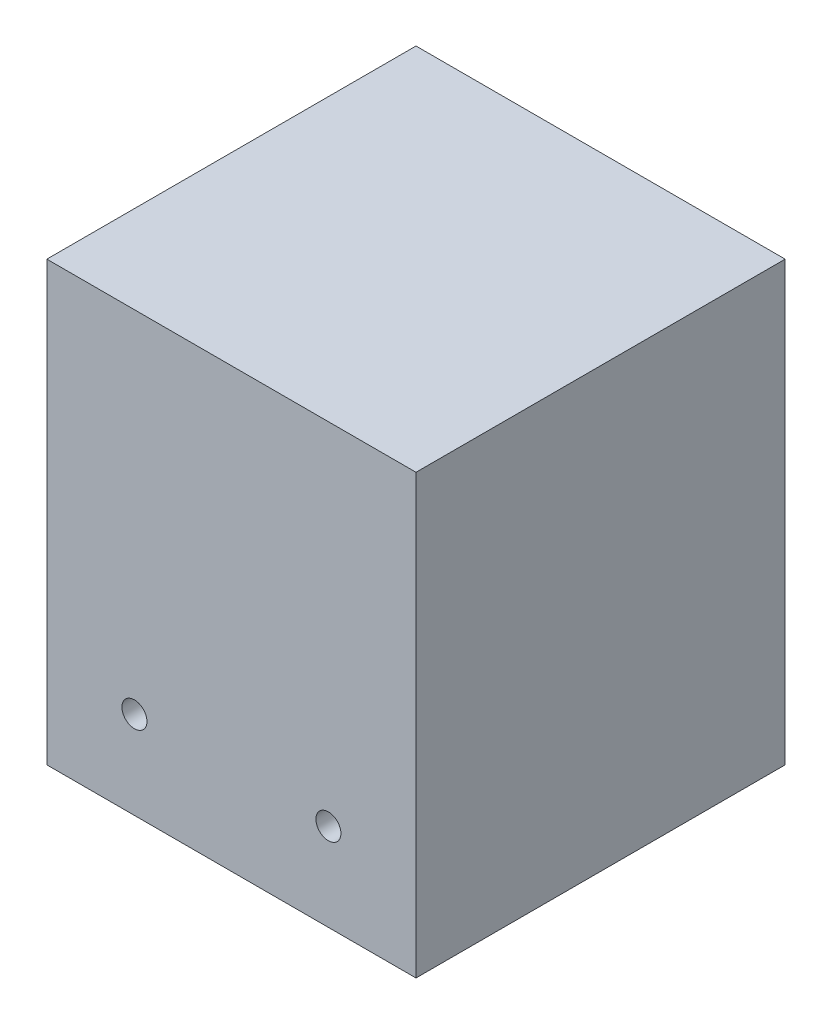
SolidWorks part; units mm, degrees
ref_plane "Plan de face" through (0, 0, 0) normal (0, 0, 1) x (1, 0, 0)
ref_plane "Plan de dessus" through (0, 0, 0) normal (0, 1, 0) x (1, 0, 0)
ref_plane "Plan de droite" through (0, 0, 0) normal (1, 0, 0) x (0, 0, -1)
sketch "Esquisse1" plane through (0, 0, 0) normal (0, 1, 0) x (1, 0, 0)
  line L1 (-29.291, 17.4415) -> (29.709, 17.4415)
  line L2 (-29.291, 17.4415) -> (-29.291, -41.5585)
  line L3 (-29.291, -41.5585) -> (29.709, -41.5585)
  line L4 (29.709, 17.4415) -> (29.709, -41.5585)
  dimension "D1" = 59
  dimension "D2" = 59
extrude "Boss.-Extru.1" add sketch "Esquisse1" along normal blind 70
sketch "Esquisse2" plane through (0, 0, 41.5585) normal (0, 0, 1) x (1, 0, 0)
  line L0 (29.709, 14) -> (15.709, 14) construction
  line L1 (29.709, 70) -> (29.709, 0) construction
  line L2 (15.709, 14) -> (-15.291, 14) construction
  line L3 (-15.291, 14) -> (-29.291, 14) construction
  line L4 (-29.291, 70) -> (-29.291, 0) construction
  line L5 (15.709, 14) -> (15.709, 0) construction
  line L6 (-29.291, 0) -> (29.709, 0) construction
  line L7 (-15.291, 14) -> (-15.291, 0) construction
  circle A0 centre (-15.291, 14) radius 2
  circle A1 centre (15.709, 14) radius 2
  dimension "D1" = 4
  dimension "D2" = 14
extrude "Enlèv. mat.-Extru.1" cut sketch "Esquisse2" against normal up to next
